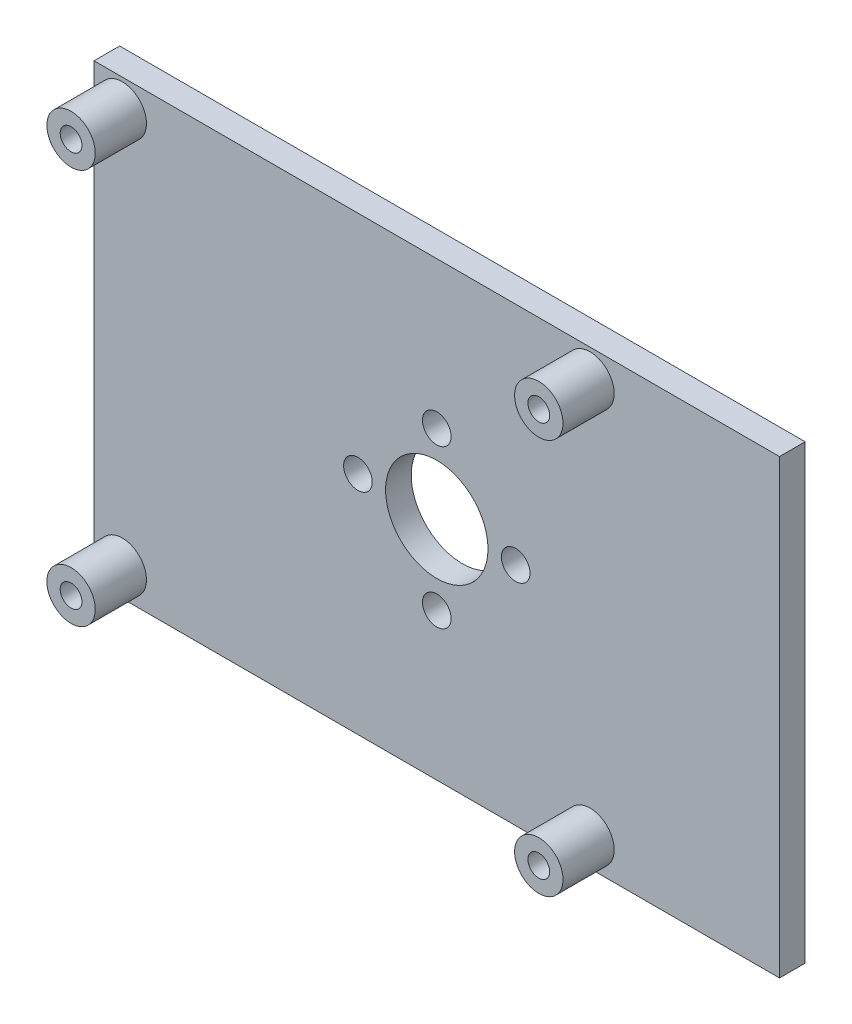
SolidWorks part; units mm, degrees
material "Copper"
ref_plane "Front Plane" through (0, 0, 0) normal (0, 0, 1) x (1, 0, 0)
ref_plane "Top Plane" through (0, 0, 0) normal (0, 1, 0) x (1, 0, 0)
ref_plane "Right Plane" through (0, 0, 0) normal (1, 0, 0) x (0, 0, -1)
sketch "Sketch1" plane through (0, 0, 0) normal (0, 0, 1) x (1, 0, 0)
  line L1 (0, 0) -> (85, 0)
  line L2 (0, 0) -> (0, 56)
  line L3 (0, 56) -> (85, 56)
  line L4 (85, 0) -> (85, 56)
  dimension "D1" = 56
  dimension "D2" = 85
extrude "Boss-Extrude1" add sketch "Sketch1" along normal blind 3.175
sketch "Sketch2" plane through (0, 0, 3.175) normal (0, 0, 1) x (1, 0, 0)
  line L0 (0, 0) -> (85, 0) construction
  line L1 (85, 0) -> (85, 56) construction
  circle A0 centre (42.5, 28) radius 6.35
  dimension "D1" = 28
  dimension "D3" = 12.7
  dimension "D2" = 42.5
extrude "Cut-Extrude1" cut sketch "Sketch2" against normal blind 3.175
sketch "Sketch3" plane through (0, 0, 3.175) normal (0, 0, 1) x (1, 0, 0)
  line L0 (0, 56) -> (0, 0) construction
  circle A0 centre (42.5, 37.779) radius 1.778
  circle A1 centre (42.5, 28) radius 6.35 construction
  dimension "D1" = 3.556
  dimension "D2" = 42.5
  dimension "D3" = 9.779
extrude "Cut-Extrude2" cut sketch "Sketch3" against normal blind 3.175
pattern_circular "CirPattern1" count 4 over 360 about axis through (42.5, 28, 3.175) along (0, 0, 1) of "Cut-Extrude2"
sketch "Sketch4" plane through (0, 0, 3.175) normal (0, 0, 1) x (1, 0, 0)
  line L0 (0, 56) -> (0, 0) construction
  line L1 (0, 0) -> (85, 0) construction
  line L2 (85, 56) -> (0, 56) construction
  circle A0 centre (3.5, 52.5) radius 3
  circle A1 centre (3.5, 52.5) radius 1.35
  circle A2 centre (3.5, 3.5) radius 3
  circle A3 centre (3.5, 3.5) radius 1.35
  circle A4 centre (61.5, 52.5) radius 3
  circle A5 centre (61.5, 52.5) radius 1.35
  circle A6 centre (61.5, 3.5) radius 3
  circle A7 centre (61.5, 3.5) radius 1.35
  dimension "D1" = 6
  dimension "D2" = 2.7
  dimension "D3" = 3.5
  dimension "D4" = 3.5
  dimension "D5" = 3.5
  dimension "D6" = 3.5
  dimension "D7" = 3.5
  dimension "D8" = 3.5
  dimension "D9" = 58
  dimension "D10" = 58
extrude "Boss-Extrude2" add sketch "Sketch4" along normal blind 6.35
